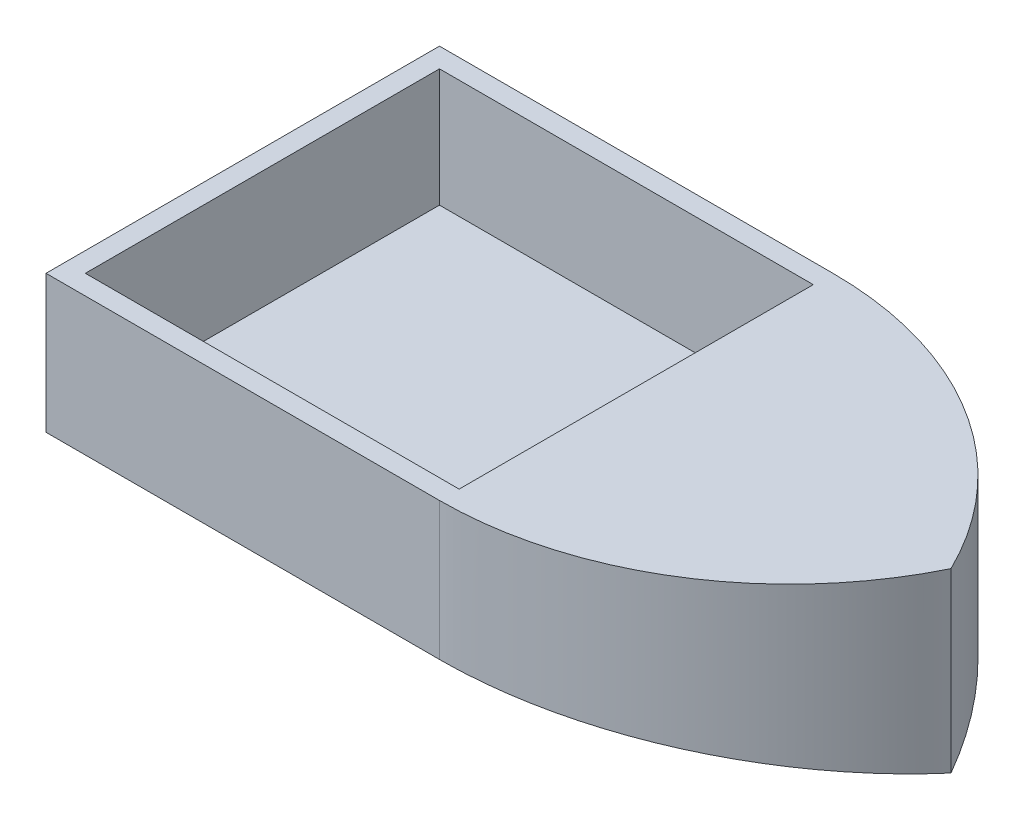
SolidWorks part; units mm, degrees
material "Polyurethane Foam Rigid"
ref_plane "Front Plane" through (0, 0, 0) normal (0, 0, 1) x (1, 0, 0)
ref_plane "Top Plane" through (0, 0, 0) normal (0, 1, 0) x (1, 0, 0)
ref_plane "Right Plane" through (0, 0, 0) normal (1, 0, 0) x (0, 0, -1)
sketch "Sketch1" plane through (0, 0, 0) normal (0, 1, 0) x (1, 0, 0)
  line L0 (0, 100) -> (0, -100)
  line L1 (0, -100) -> (200, -100)
  line L2 (0, 0) -> (360, 0) construction
  line L3 (0, 100) -> (200, 100)
  arc A0 (200, -100) -> (360, 0) centre (200, 78) ccw
  arc A1 (200, 100) -> (360, 0) centre (200, -78) cw
  dimension "D4" = 200
  dimension "D1" = 100
  dimension "D3" = 360
extrude "Boss-Extrude1" add sketch "Sketch1" along normal blind 90
sketch "Sketch2" plane through (0, 0, 0) normal (-1, 0, 0) x (0, 0, 1)
  line L1 (-100, 90) -> (-100, 0) construction
  line L3 (100, 90) -> (100, 0) construction
  line L7 (0, 0) -> (100, 20)
  line L8 (0, 0) -> (-100, 20)
  line L9 (-100, 20) -> (-100, 0)
  line L10 (-100, 0) -> (0, 0)
  line L11 (100, 20) -> (100, 0)
  line L12 (100, 0) -> (0, 0)
  line M3 (-100, 0) -> (100, 0)
  line M6 (-100, 90) -> (-100, 0)
  dimension "D1" = 20
  dimension "D2" = 20
extrude "Cut-Extrude1" cut sketch "Sketch2" against normal through all contours L8 M3 M6 | L7 L11 L12 region at (0, 6.6667, -66.6667)
shell "Shell3" thickness 10 removed face at (157.7359, 90, 0)
sketch "Sketch6" plane through (0, 90, 0) normal (0, 1, 0) x (1, 0, 0)
  line L0 (200, 90) -> (200, -90)
  arc A0 (200, -90) -> (348.7952, 0) centre (200, 78) ccw
  arc A1 (348.7952, 0) -> (200, 90) centre (200, -78) ccw
  dimension "D1" = 168
  dimension "D2" = 168
extrude "Boss-Extrude2" add sketch "Sketch6" against normal blind 10
sketch "Sketch9" plane through (0, 0, 0) normal (-1, 0, 0) x (0, 0, 1)
  line L0 (-90, 80) -> (-90, 20)
  line L1 (-90, 20) -> (90, 20)
  line L2 (90, 20) -> (90, 80)
  line L3 (90, 80) -> (-90, 80)
  line L4 (-100, 90) -> (-100, 20) construction
  line L5 (100, 90) -> (100, 20) construction
  line L6 (-100, 90) -> (100, 90) construction
  dimension "D1" = 10
  dimension "D2" = 10
  dimension "D3" = 20
  dimension "D4" = 10
extrude "Boss-Extrude3" add sketch "Sketch9" against normal blind 220 contours L2 L3 L0 L1 region at (0, 50, 0)
extrude "Cut-Extrude3" cut sketch "Sketch9<4>" against normal blind 200
sketch "Sketch9<4>" plane through (0, 0, 0) normal (-1, 0, 0) x (0, 0, 1) same geometry as "Sketch9"
extrude "Boss-Extrude5" add sketch "Sketch9<5>" against normal blind 10
sketch "Sketch9<5>" plane through (0, 0, 0) normal (-1, 0, 0) x (0, 0, 1) same geometry as "Sketch9"
sketch "Sketch10" plane through (0, 90, 0) normal (0, 1, 0) x (1, 0, 0)
  line L0 (10, 90) -> (200, 90)
  line L1 (200, 90) -> (200, -90)
  line L2 (200, -90) -> (10, -90)
  line L3 (10, -90) -> (10, 90)
extrude "Boss-Extrude6" add sketch "Sketch10" against normal blind 70
extrude "Cut-Extrude4" cut sketch "Sketch10<2>" against normal blind 30
sketch "Sketch10<2>" plane through (0, 90, 0) normal (0, 1, 0) x (1, 0, 0) same geometry as "Sketch10"
extrude "Cut-Extrude5" cut sketch "Sketch10<3>" against normal blind 50
sketch "Sketch10<3>" plane through (0, 90, 0) normal (0, 1, 0) x (1, 0, 0) same geometry as "Sketch10"
extrude "Cut-Extrude6" cut sketch "Sketch10<4>" against normal blind 60
sketch "Sketch10<4>" plane through (0, 90, 0) normal (0, 1, 0) x (1, 0, 0) same geometry as "Sketch10"
